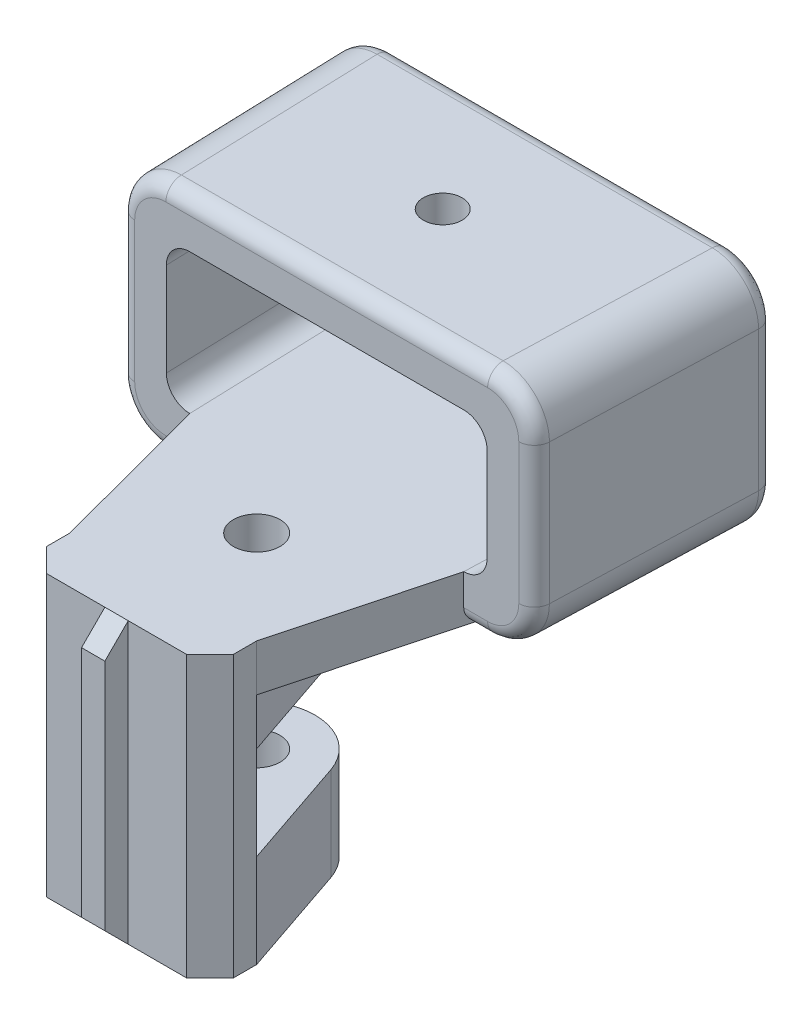
SolidWorks part; units mm, degrees
ref_plane "정면" through (0, 0, 0) normal (0, 0, 1) x (1, 0, 0)
ref_plane "윗면" through (0, 0, 0) normal (0, 1, 0) x (1, 0, 0)
ref_plane "우측면" through (0, 0, 0) normal (1, 0, 0) x (0, 0, -1)
sketch "스케치1" plane through (0, 0, 0) normal (0, 1, 0) x (1, 0, 0)
  line L0 (-12, -12) -> (12, -12)
  line L1 (12, -12) -> (7.101, 2.4135)
  line L2 (-12, -12) -> (-7.101, 2.4135)
  circle A0 centre (0, 0) radius 3
  arc A1 (7.101, 2.4135) -> (-7.101, 2.4135) centre (0, 0) ccw
  point P9 (0, -12)
  dimension "D1" = 6
  dimension "D2" = 15
  dimension "D3" = 24
  dimension "D4" = 12
extrude "보스-돌출1" add sketch "스케치1" along normal blind 12
sketch "스케치2" plane through (0, 0, 0) normal (0, 1, 0) x (1, 0, 0)
  line L0 (-12, -12) -> (12, -12)
  line L1 (12, -12) -> (12, -18)
  line L2 (12, -18) -> (-12, -18)
  line L3 (-12, -18) -> (-12, -12)
  dimension "D1" = 6
extrude "보스-돌출2" add sketch "스케치2" along normal blind 36
sketch "스케치3" plane through (0, 36, 0) normal (0, 1, 0) x (1, 0, 0)
  line L3 (-7.101, 2.4135) -> (-12, -12)
  line L4 (-12, -12) -> (12, -12)
  line L5 (12, -12) -> (7.101, 2.4135)
  line L6 (-7.101, 2.4135) -> (-12, -12)
  line L7 (-12, -12) -> (12, -12)
  line L8 (12, -12) -> (7.101, 2.4135)
  circle A0 centre (0, 0) radius 3 construction
  arc A1 (7.101, 2.4135) -> (-7.101, 2.4135) centre (0, 0) ccw
  arc A2 (7.101, 2.4135) -> (-7.101, 2.4135) centre (0, 0) ccw
  circle A3 centre (0, 0) radius 3
  dimension "D1" = 0
extrude "보스-돌출3" add sketch "스케치3" against normal blind 12
sketch "스케치5" plane through (0, 36, 0) normal (0, 1, 0) x (1, 0, 0)
  line L0 (-20.6, 9) -> (20.6, 9) construction
  line L1 (20.6, 9) -> (21.6, 39)
  line L2 (21.6, 39) -> (-21.6, 39)
  line L3 (-21.6, 39) -> (-20.6, 9)
  line L4 (-20.6, 9) -> (-12, -12)
  line L5 (-12, -12) -> (12, -12)
  line L6 (12, -12) -> (20.6, 9)
  circle A0 centre (0, 0) radius 3 construction
  circle A1 centre (0, 0) radius 3
  point P2 (0, 9)
  point P5 (0, 39)
  dimension "D1" = 41.2
  dimension "D2" = 43.2
  dimension "D3" = 30
  dimension "D4" = 9
extrude "보스-돌출5" add sketch "스케치5" against normal blind 6
sketch "스케치8" plane through (0, 30, 0) normal (0, -1, 0) x (1, 0, 0)
  line L0 (-27.6033, -39) -> (-21.6, -39)
  line L1 (-20.6, -9) -> (-26.6033, -9)
  line L2 (20.6, -9) -> (26.6033, -9)
  line L5 (26.5967, -8.8001) -> (27.5967, -38.8001)
  line L6 (26.6033, -9) -> (27.6033, -39)
  line L7 (-20.6, -9) -> (-21.6, -39)
  line L8 (-27.5967, -38.8001) -> (-26.5967, -8.8001)
  line L9 (-27.6033, -39) -> (-26.6033, -9)
  line L10 (21.6, -39) -> (20.6, -9)
  line L11 (21.6, -39) -> (27.6033, -39)
  dimension "D1" = 6
  dimension "D2" = 6
extrude "보스-돌출7" add sketch "스케치8" against normal blind 30
sketch "스케치9" plane through (0, 0, 0) normal (1, 0, 0) x (0, 0, -1)
  line L0 (33.7, 30) -> (6.7, 25)
  line L1 (39, 30) -> (9, 30) construction
  line L2 (6.7, 25) -> (6.7, 30)
  line L3 (2.4135, 30) -> (7.5, 30) construction
  line L4 (6.7, 30) -> (33.7, 30)
  dimension "D1" = 27
  dimension "D2" = 5
  dimension "D3" = 6.7
extrude "보스-돌출8" add sketch "스케치9" along normal mid plane 6
sketch "스케치10" plane through (0, 60, 0) normal (0, 1, 0) x (1, 0, 0)
  line L0 (20.6, 9) -> (21.6, 39) construction
  line L2 (20.6, 9) -> (21.6, 39)
  line L4 (-21.7, 39) -> (21.6, 39)
  line L6 (-20.6, 9) -> (20.6, 9)
  line L7 (-21.7, 39) -> (-20.6, 9)
  circle A0 centre (-0.1013, 24) radius 2.5
  dimension "D1" = 5
  dimension "D2" = 15
extrude "보스-돌출9" add sketch "스케치10" against normal blind 6
fillet "필렛1" radius 3 4 edges at (-21.1, 54, -24) (-21.1, 36, -24) (21.1, 36, -24) (21.1, 54, -24)
fillet "필렛2" radius 6 4 edges at (-27.1033, 60, -24) (-27.1033, 30, -24) (27.1033, 30, -24) (27.1033, 60, -24)
sketch "스케치11" plane through (0, 0, 0) normal (1, 0, 0) x (0, 0, -1)
  line L0 (-12, 24) -> (-12, 12)
  line L1 (-12, 12) -> (-9, 12)
  line L2 (-9, 12) -> (-9, 24)
  line L3 (-12, 24) -> (2.4135, 24) construction
  line L4 (-9, 24) -> (-12, 24)
  line L5 (-18, 36) -> (-18, 0)
  line L6 (-18, 0) -> (-21, 3)
  line L7 (-21, 3) -> (-21, 33)
  line L8 (-21, 33) -> (-18, 36)
  dimension "D1" = 3
  dimension "D2" = 3
  dimension "D3" = 3
  dimension "D4" = 3
extrude "보스-돌출10" add sketch "스케치11" along normal mid plane 3
sketch "스케치12" plane through (0, 0, -9) normal (0, 0, 1) x (1, 0, 0)
  line L0 (-38.0438, 36) -> (35.8108, 36)
  line L1 (35.8108, 36) -> (35.8108, 40.7102)
  line L2 (35.8108, 40.7102) -> (-38.0438, 40.7102)
  line L3 (-38.0438, 40.7102) -> (-38.0438, 36)
extrude "컷-돌출1" cut sketch "스케치12" along normal blind 13
sketch "스케치13" plane through (0, 36, 0) normal (0, 1, 0) x (1, 0, 0)
  line L0 (-17.5983, 9) -> (-12, -12)
  line L1 (17.5983, 9) -> (12, -12)
  line L2 (-17.5983, 9) -> (-22.9421, 9)
  line L3 (-26.6033, 9) -> (-20.6, 9) construction
  line L4 (-22.9421, 9) -> (-14.2209, -12)
  line L5 (-14.2209, -12) -> (-12, -12)
  line L6 (12, -12) -> (13.7495, -12)
  line L7 (13.7495, -12) -> (23.6017, 9)
  line L8 (20.6, 9) -> (26.6033, 9) construction
  line L9 (23.6017, 9) -> (17.5983, 9)
extrude "컷-돌출2" cut sketch "스케치13" against normal blind 13
fillet "필렛3" radius 2 17 edges at (19.0992, 30, -9) (24.845, 31.7574, -9) (26.6033, 45, -9) (24.845, 58.2426, -9) (-19.0992, 30, -9) (-24.845, 31.7574, -9) (-26.6033, 45, -9) (-24.845, 58.2426, -9) (-25.845, 58.2426, -39) (-27.6033, 45, -39) (-25.845, 31.7574, -39) (0, 30, -39) (25.845, 31.7574, -39) (27.6033, 45, -39) (25.845, 58.2426, -39) (0, 60, -9) (0, 60, -39)
chamfer "모따기1" distance 3 angle 45 2 edges at (12, 18, 18) (-12, 18, 18)
